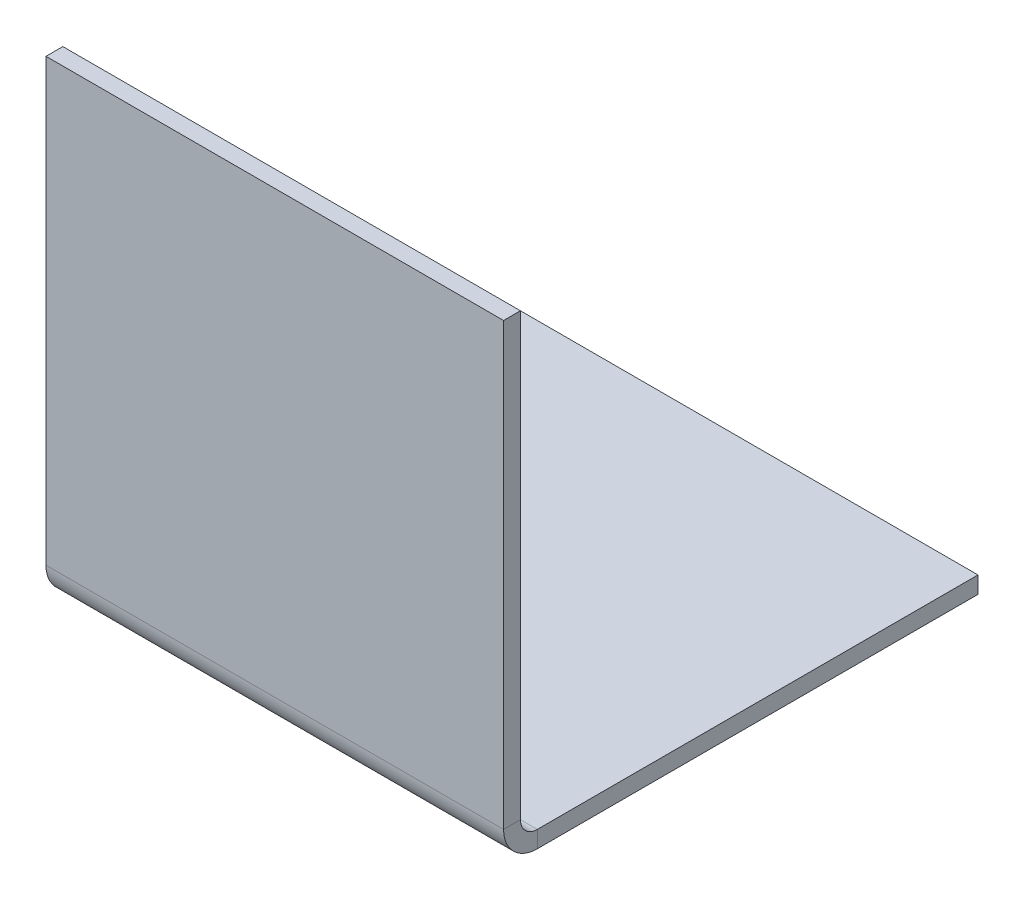
SolidWorks part; units mm, degrees
note: The reader was unsure of these and kept them because the rebuilt part matched: flange length of "Edge-Flange1".
ref_plane "Front Plane" through (0, 0, 0) normal (0, 0, 1) x (1, 0, 0)
ref_plane "Top Plane" through (0, 0, 0) normal (0, 1, 0) x (1, 0, 0)
ref_plane "Right Plane" through (0, 0, 0) normal (1, 0, 0) x (0, 0, -1)
sketch "Sketch1" plane through (0, 0, 0) normal (0, 1, 0) x (1, 0, 0)
  line L1 (-10, -10) -> (10, -10)
  line L2 (-10, -10) -> (-10, 10)
  line L3 (-10, 10) -> (10, 10)
  line L4 (10, -10) -> (10, 10)
  line L5 (-10, -10) -> (10, 10) construction
  line L6 (-10, 10) -> (10, -10) construction
  point P0 (0, 0)
  dimension "D1" = 20
  dimension "D2" = 20
base flange "Base-Flange1" sketch "Sketch1" thickness 0.7366 reverse thickness direction no parameters "D1"=0.7366
edge flange "Edge-Flange1" sketch "Sketch8" flange angle 90 flange length 20 flange position material outside bend radius 0.7366 thickness 0.7366 relief rectangular parameters "D6"=10
sketch "Sketch8" plane through (0, 0, 10) normal (0, 0, 1) x (1, 0, 0)
  line L0 (-10, 0) -> (10, 0) construction
  line L1 (-10, 0) -> (10, 0)
  line L2 (-10, 0) -> (-10, 20)
  line L3 (-10, 20) -> (10, 20)
  line L4 (10, 20) -> (10, 0)
bend "EdgeBend1" bend radius 0.7366 bend angle 90 parameters "D5"=1
sketch "Bend-Lines1" plane through (0, 0, 0) normal (0, 1, 0) x (1, 0, 0)
sketch "Bounding-Box1" plane through (0, 0, 0) normal (0, 1, 0) x (1, 0, 0)
sheet metal parameters "Sheet-Metal1" thickness 0.7366 parameters "D1"=0.7366
flat pattern "Flat-Pattern1" [suppressed]
sketch "Bend-Lines2" plane through (0, 0, 0) normal (0, 1, 0) x (1, 0, 0)
sketch "Bounding-Box2" [suppressed] plane through (0, 0, 0) normal (0, 1, 0) x (1, 0, 0)
sheet metal parameters "Sheet-Metal2" thickness 0.7366 parameters "D1"=0.7366
flat pattern "Flat-Pattern1" [suppressed]
sketch "Bend-Lines2" plane through (0, 0, 0) normal (0, 1, 0) x (1, 0, 0)
sketch "Bounding-Box2" [suppressed] plane through (0, 0, 0) normal (0, 1, 0) x (1, 0, 0)
bend of the flat pattern "Flatten-<EdgeBend1>1"
